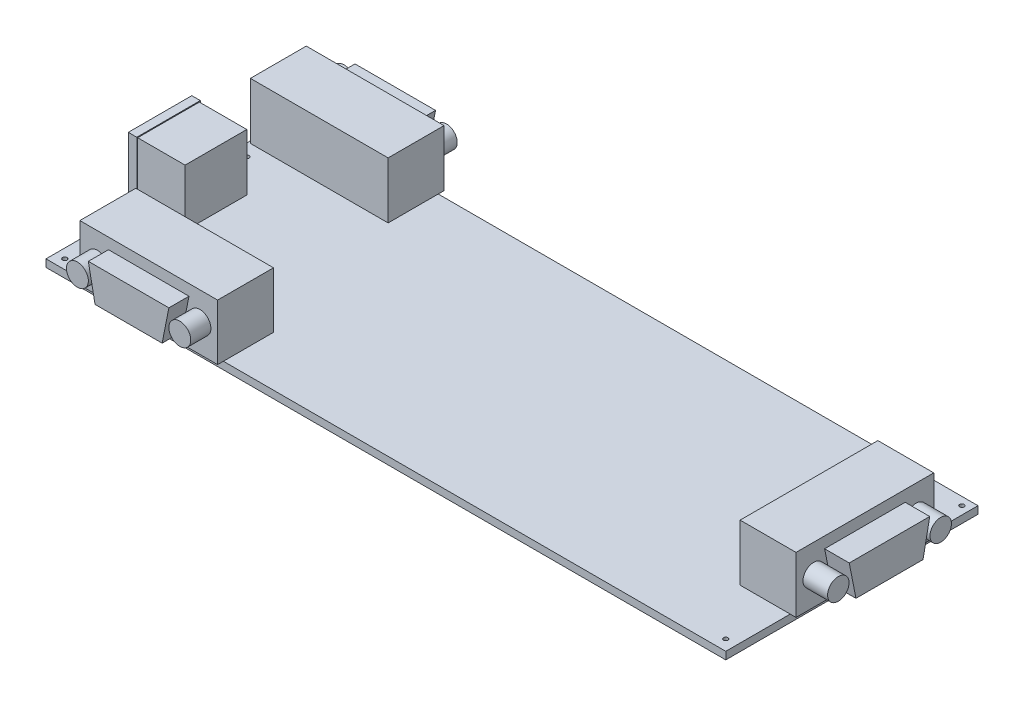
SolidWorks part; units mm, degrees
ref_plane "Front Plane" through (0, 0, 0) normal (0, 0, 1) x (1, 0, 0)
ref_plane "Top Plane" through (0, 0, 0) normal (0, 1, 0) x (1, 0, 0)
ref_plane "Right Plane" through (0, 0, 0) normal (1, 0, 0) x (0, 0, -1)
sketch "Sketch1" plane through (0, 0, 0) normal (0, 1, 0) x (1, 0, 0)
  line L1 (-76, -28.2) -> (76, -28.2)
  line L2 (-76, -28.2) -> (-76, 28.2)
  line L3 (-76, 28.2) -> (76, 28.2)
  line L4 (76, -28.2) -> (76, 28.2)
  line L5 (-76, -28.2) -> (76, 28.2) construction
  line L6 (-76, 28.2) -> (76, -28.2) construction
  point P0 (0, 0)
  dimension "D1" = 152
  dimension "D2" = 56.4
extrude "Boss-Extrude1" add sketch "Sketch1" along normal blind 1.67
sketch "Sketch3" plane through (0, 1.67, 0) normal (0, 1, 0) x (1, 0, 0)
  line L0 (-76, -28.2) -> (76, -28.2) construction
  line L1 (64.8, 17.01) -> (77.3, 17.01)
  line L2 (64.8, 17.01) -> (64.8, -13.79)
  line L3 (64.8, -13.79) -> (77.3, -13.79)
  line L4 (77.3, 17.01) -> (77.3, -13.79)
  line L5 (64.8, 17.01) -> (77.3, -13.79) construction
  line L6 (64.8, -13.79) -> (77.3, 17.01) construction
  line L7 (76, -28.2) -> (76, 28.2) construction
  point P0 (71.05, 1.61)
  dimension "D1" = 30.8
  dimension "D2" = 12.5
  dimension "D3" = 14.41
  dimension "D4" = 11.2
extrude "Boss-Extrude2" add sketch "Sketch3" along normal blind 12.6
sketch "Sketch4" plane through (77.3, 0, 0) normal (1, 0, 0) x (0, 0, -1)
  line L0 (-13.79, 7.97) -> (17.01, 7.97) construction
  line L1 (-13.79, 14.27) -> (-13.79, 1.67) construction
  line L2 (17.01, 14.27) -> (17.01, 1.67) construction
  line L3 (1.61, 14.27) -> (1.61, 1.67) construction
  line L4 (-13.79, 14.27) -> (17.01, 14.27) construction
  line L5 (-13.79, 1.67) -> (17.01, 1.67) construction
  line L6 (-7.39, 11.77) -> (10.61, 11.77)
  line L7 (10.61, 11.77) -> (9.11, 4.17)
  line L8 (9.11, 4.17) -> (-5.89, 4.17)
  line L9 (-5.89, 4.17) -> (-7.39, 11.77)
  circle A0 centre (-9.84, 7.97) radius 2.4
  circle A1 centre (13.06, 7.97) radius 2.4
  dimension "D1" = 22.9
  dimension "D2" = 4.8
  dimension "D3" = 18
  dimension "D4" = 15
  dimension "D5" = 3.8
  dimension "D6" = 3.8
extrude "Boss-Extrude3" add sketch "Sketch4" along normal blind 5.5
sketch "Sketch5" plane through (0, 1.67, 0) normal (0, 1, 0) x (1, 0, 0)
  line L0 (76, 28.2) -> (-76, 28.2) construction
  line L1 (-75.5, 17) -> (-44.7, 17)
  line L2 (-75.5, 17) -> (-75.5, 29.5)
  line L3 (-75.5, 29.5) -> (-44.7, 29.5)
  line L4 (-44.7, 17) -> (-44.7, 29.5)
  line L5 (-75.5, 17) -> (-44.7, 29.5) construction
  line L6 (-75.5, 29.5) -> (-44.7, 17) construction
  line L7 (-76, 28.2) -> (-76, -28.2) construction
  point P2 (-60.1, 23.25)
  dimension "D1" = 12.5
  dimension "D2" = 11.2
  dimension "D3" = 30.8
  dimension "D4" = 0.5
extrude "Boss-Extrude4" add sketch "Sketch5" along normal blind 12.6
sketch "Sketch6" plane through (0, 1.67, 0) normal (0, 1, 0) x (1, 0, 0)
  line L0 (-76, -28.2) -> (76, -28.2) construction
  line L1 (-36.33, -17) -> (-67.13, -17)
  line L2 (-36.33, -17) -> (-36.33, -29.5)
  line L3 (-36.33, -29.5) -> (-67.13, -29.5)
  line L4 (-67.13, -17) -> (-67.13, -29.5)
  line L5 (-36.33, -17) -> (-67.13, -29.5) construction
  line L6 (-36.33, -29.5) -> (-67.13, -17) construction
  line L7 (-76, 28.2) -> (-76, -28.2) construction
  point P0 (-51.73, -23.25)
  dimension "D1" = 12.5
  dimension "D2" = 30.8
  dimension "D3" = 11.2
  dimension "D4" = 8.87
extrude "Boss-Extrude5" add sketch "Sketch6" along normal blind 12.5
sketch "Sketch7" plane through (0, 0, 29.5) normal (0, 0, 1) x (1, 0, 0)
  line L0 (-67.13, 7.92) -> (-36.33, 7.92) construction
  line L1 (-67.13, 14.17) -> (-67.13, 1.67) construction
  line L2 (-36.33, 14.17) -> (-36.33, 1.67) construction
  line L3 (-51.73, 14.17) -> (-51.73, 1.67) construction
  line L4 (-67.13, 14.17) -> (-36.33, 14.17) construction
  line L5 (-67.13, 1.67) -> (-36.33, 1.67) construction
  line L6 (-60.73, 11.72) -> (-42.73, 11.72)
  line L7 (-42.73, 11.72) -> (-44.23, 4.12)
  line L8 (-44.23, 4.12) -> (-59.23, 4.12)
  line L9 (-59.23, 4.12) -> (-60.73, 11.72)
  circle A0 centre (-63.18, 7.92) radius 2.45
  circle A1 centre (-40.28, 7.92) radius 2.45
  dimension "D1" = 4.9
  dimension "D2" = 22.9
  dimension "D3" = 15
  dimension "D4" = 18
  dimension "D5" = 3.8
  dimension "D6" = 3.8
extrude "Boss-Extrude6" add sketch "Sketch7" along normal blind 4.5
sketch "Sketch9" plane through (0, 0, -29.5) normal (0, 0, -1) x (-1, 0, 0)
  line L0 (44.7, 7.97) -> (75.5, 7.97) construction
  line L1 (60.1, 14.27) -> (60.1, 1.67) construction
  line L2 (51.1, 11.77) -> (69.1, 11.77)
  line L3 (69.1, 11.77) -> (67.6, 4.17)
  line L4 (67.6, 4.17) -> (52.6, 4.17)
  line L5 (52.6, 4.17) -> (51.1, 11.77)
  line L6 (44.7, 1.67) -> (75.5, 1.67) construction
  line L7 (44.7, 14.27) -> (75.5, 14.27) construction
  line L8 (44.7, 14.27) -> (44.7, 1.67) construction
  line L9 (75.5, 14.27) -> (75.5, 1.67) construction
  circle A0 centre (48.65, 7.97) radius 2.4
  circle A1 centre (71.55, 7.97) radius 2.4
  dimension "D1" = 4.8
  dimension "D6" = 22.9
  dimension "D2" = 15
  dimension "D3" = 18
  dimension "D4" = 3.8
  dimension "D5" = 3.8
extrude "Boss-Extrude7" add sketch "Sketch9" along normal blind 4.5
sketch "Sketch10" plane through (0, 1.67, 0) normal (0, 1, 0) x (1, 0, 0)
  line L0 (-76, 28.2) -> (-76, -28.2) construction
  line L1 (-76.5, -7.2) -> (-65.9, -7.2)
  line L2 (-76.5, -7.2) -> (-76.5, 6.6)
  line L3 (-76.5, 6.6) -> (-65.9, 6.6)
  line L4 (-65.9, -7.2) -> (-65.9, 6.6)
  line L5 (-76.5, -7.2) -> (-65.9, 6.6) construction
  line L6 (-76.5, 6.6) -> (-65.9, -7.2) construction
  line L7 (-76, -28.2) -> (-67.13, -28.2) construction
  point P0 (-71.2, -0.3)
  point P7 (-71.565, -28.2)
  dimension "D1" = 13.8
  dimension "D2" = 10.6
  dimension "D3" = 10.1
  dimension "D4" = 21
extrude "Boss-Extrude8" add sketch "Sketch10" along normal blind 12.7
sketch "Sketch12" plane through (-76.5, 0, 0) normal (-1, 0, 0) x (0, 0, 1)
  line L0 (7.4, 14.57) -> (-6.8, 14.57)
  line L1 (-6.8, 14.57) -> (-6.8, 1.47)
  line L2 (-6.8, 1.47) -> (7.4, 1.47)
  line L3 (7.4, 1.47) -> (7.4, 14.57)
  line L4 (-6.6, 1.67) -> (7.2, 1.67)
  line L5 (7.2, 1.67) -> (7.2, 14.37)
  line L6 (7.2, 14.37) -> (-6.6, 14.37)
  line L7 (-6.6, 14.37) -> (-6.6, 1.67)
  line L8 (-6.6, 1.67) -> (7.2, 1.67) construction
  line L9 (7.2, 1.67) -> (7.2, 14.37) construction
  line L10 (7.2, 14.37) -> (-6.6, 14.37) construction
  line L11 (-6.6, 14.37) -> (-6.6, 1.67) construction
  dimension "D1" = 0
  dimension "D2" = 0.2
extrude "Boss-Extrude9" add sketch "Sketch12" along normal blind 1.9
sketch "Sketch13" plane through (0, 0, 0) normal (0, -1, 0) x (1, 0, 0)
  line L0 (76, 28.2) -> (76, -28.2) construction
  line L1 (31.5, 20) -> (36.5, 20)
  line L2 (31.5, 20) -> (31.5, -25.8)
  line L3 (31.5, -25.8) -> (36.5, -25.8)
  line L4 (36.5, 20) -> (36.5, -25.8)
  line L5 (31.5, 20) -> (36.5, -25.8) construction
  line L6 (31.5, -25.8) -> (36.5, 20) construction
  line L7 (-76, 28.2) -> (76, 28.2) construction
  line L8 (76, -28.2) -> (-76, -28.2) construction
  point P0 (34, -2.9)
  dimension "D1" = 42
  dimension "D2" = 8.2
  dimension "D3" = 2.4
  dimension "D4" = 5
extrude "Boss-Extrude10" add sketch "Sketch13" along normal blind 2.7
sketch "Sketch14" plane through (0, 1.67, 0) normal (0, 1, 0) x (1, 0, 0)
  line L0 (76, 17.01) -> (76, 28.2) construction
  line L1 (76, 28.2) -> (-44.7, 28.2) construction
  line L2 (76, -28.2) -> (76, -13.79) construction
  line L3 (-36.33, -28.2) -> (76, -28.2) construction
  line L4 (-76, -28.2) -> (-67.13, -28.2) construction
  line L5 (-76, -7.2) -> (-76, -28.2) construction
  line L6 (-76, 28.2) -> (-76, 6.6) construction
  circle A0 centre (74.2, 26.4) radius 0.5
  circle A1 centre (73.6, -25.8) radius 0.5
  circle A2 centre (-73.9, -26.1) radius 0.5
  circle A3 centre (-73.3, 14) radius 0.5
  dimension "D1" = 1
  dimension "D5" = 2.4
  dimension "D8" = 2.7
  dimension "D9" = 14.2
  dimension "D2" = 1.8
  dimension "D3" = 1.8
  dimension "D4" = 2.4
  dimension "D6" = 2.1
  dimension "D7" = 2.1
extrude "Cut-Extrude1" cut sketch "Sketch14" against normal through all
